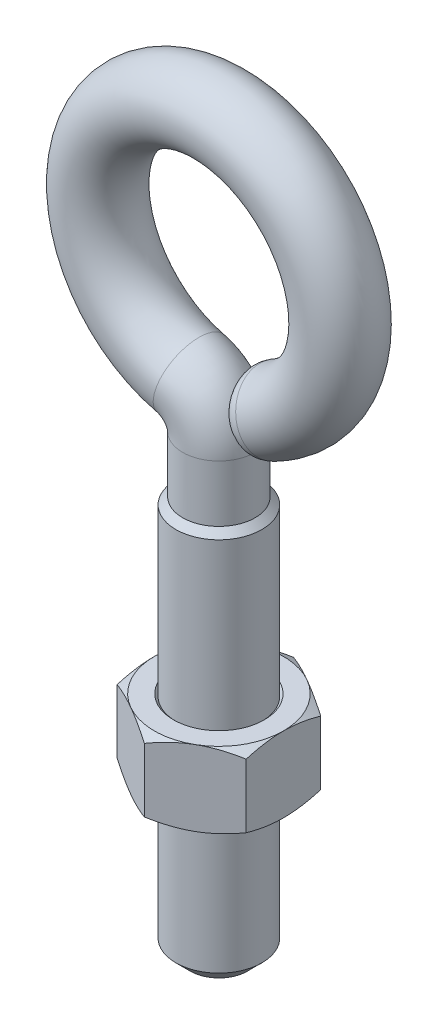
SolidWorks part; units mm, degrees
ref_plane "Front Plane" through (0, 0, 0) normal (0, 0, 1) x (1, 0, 0)
ref_plane "Top Plane" through (0, 0, 0) normal (0, 1, 0) x (1, 0, 0)
ref_plane "Right Plane" through (0, 0, 0) normal (1, 0, 0) x (0, 0, -1)
sketch "Sketch1" plane through (0, 0, 0) normal (0, 0, 1) x (1, 0, 0)
  line L0 (0, -8.636) -> (0, -34.036) construction
  line L1 (-2.413, -34.036) -> (2.413, -34.036) construction
  line L2 (0, -11.811) -> (2.413, -11.811) construction
  line L3 (0, -8.636) -> (0, -4.7625) construction
  line L4 (-2.032, -11.811) -> (2.032, -11.811) construction
  line L5 (2.032, -11.811) -> (2.032, -8.636) construction
  line L7 (2.413, -34.036) -> (2.413, -11.811) construction
  line L8 (2.032, -8.636) -> (0, -8.636) construction
  circle A0 centre (0, 0) radius 8.8265 construction
  circle A1 centre (0, 6.7945) radius 2.032 construction
  circle A2 centre (0, 0) radius 4.7625 construction
  point P9 (0, -8.636)
  point P10 (0, 8.8265)
  point P11 (0, 4.7625)
  point P14 (0, -34.036)
  point P24 (0, -11.811)
  dimension "A" = 4.064
  dimension "Eye Dia." = 9.525
  dimension "Shank Lg." = 25.4
  dimension "Thread OD" = 4.826
  dimension "Thread Lg." = 22.225
  dimension "Overall Lg." = 42.8625
  dimension "OD" = 17.4625
  dimension "Wire OD." = 4.064
sketch "Sketch2" plane through (0, 0, 0) normal (0, 1, 0) x (1, 0, 0)
  circle A0 centre (0, 0) radius 2.413
extrude "Boss-Extrude1" add sketch "Sketch2" against normal up to vertex (34.036 mm away) from vertex up to point (0, -34.036, 0) starting at point (0, -11.811, 0)
sketch "Sketch3" plane through (0, -34.036, 0) normal (0, -1, 0) x (1, 0, 0)
  circle A1 centre (0, 0) radius 2.413
  circle A2 centre (0, 0) radius 2.413
  point P0 (2.413, 0)
  point P1 (0, -2.413)
  dimension "D1" = 0
curve "Helix/Spiral1" [suppressed] pitch 1.0583 height 23.2833 turns 22 parameters "Pitch"=1.0583
sketch "Sketch4" plane through (0, 0, 0) normal (0, 0, 1) x (1, 0, 0)
  line L0 (2.5276, -33.9699) -> (2.5276, -35.0282) construction
  line L1 (2.5276, -35.0282) -> (1.611, -34.499) construction
  line L2 (1.611, -34.499) -> (2.5276, -33.9699) construction
  line L3 (1.7256, -34.4329) -> (1.7256, -34.5652) construction
  line L4 (2.413, -34.036) -> (2.413, -34.962) construction
  line L5 (1.611, -34.499) -> (1.7256, -34.499) construction
  line L6 (2.413, -34.499) -> (2.5276, -34.499) construction
  line L7 (2.4703, -34.0029) -> (1.7256, -34.4329)
  line L8 (1.7256, -34.4329) -> (1.7256, -34.5652)
  line L9 (1.7256, -34.5652) -> (2.4703, -34.9951)
  line L10 (2.4703, -34.9951) -> (2.4703, -34.0029)
  point P13 (2.4703, -34.499)
  dimension "D1" = 1.0583
  dimension "D2" = 0.1323
sweep "Cut-Sweep1" [suppressed] cut profiles "Sketch4" path "Helix/Spiral1"
sketch "Sketch5" plane through (0, -34.036, 0) normal (0, -1, 0) x (1, 0, 0)
  circle A0 centre (0, 0) radius 1.611
extrude "Cut-Extrude1" cut sketch "Sketch5" against normal up to vertex (22.225 mm away) draft 45 flip side to cut up to point (0, -11.811, 0)
sketch "Sketch7" plane through (0, -11.811, 0) normal (0, 1, 0) x (1, 0, 0)
  circle A0 centre (0, 0) radius 2.032
sketch "Sketch8" plane through (0, 0, 0) normal (0, 0, 1) x (1, 0, 0)
  line L0 (0, -8.636) -> (0, -34.036) construction
  line L1 (0, -8.636) -> (0, -11.811)
  line L2 (0, -8.636) -> (0, -4.7625) construction
  arc A0 (2.0092, -6.4906) -> (-1.599, -6.6037) centre (0, 0) ccw
  arc A1 (0, -8.636) -> (-1.599, -6.6037) centre (-2.091, -8.636) ccw
  circle A3 centre (0, -6.7945) radius 2.032 construction
sketch "Sketch6" plane through (0, -11.811, 0) normal (0, 1, 0) x (1, 0, 0)
  circle A0 centre (0, 0) radius 2.032
extrude "Cut-Extrude2" cut sketch "Sketch6" against normal up to vertex (22.225 mm away) draft 45 flip side to cut up to point (0, -34.036, 0)
sweep "Sweep1" add profiles "Sketch7" path "Sketch8"
fillet "Fillet1" radius 1.2065 1 edges at (2.0092, -6.4906, 2.032)
sketch "Sketch9" plane through (0, -34.036, 0) normal (0, -1, 0) x (1, 0, 0)
  line L1 (0, 4.1794) -> (-3.6195, 2.0897)
  line L2 (-3.6195, 2.0897) -> (-3.6195, -2.0897)
  line L3 (-3.6195, -2.0897) -> (0, -4.1794)
  line L4 (0, -4.1794) -> (3.6195, -2.0897)
  line L5 (3.6195, -2.0897) -> (3.6195, 2.0897)
  line L6 (3.6195, 2.0897) -> (0, 4.1794)
  circle A0 centre (0, 0) radius 3.6195 construction
  circle A1 centre (0, 0) radius 2.413
  dimension "Nut Wd." = 7.239
extrude "Boss-Extrude2" add sketch "Sketch9" against normal blind 4.2227 from offset 8.4455 separate body offset against normal yes
sketch "Sketch10" plane through (0, 0, 0) normal (1, 0, 0) x (0, 0, -1)
  line L0 (-3.6195, -21.3677) -> (-4.7394, -21.3677)
  line L1 (-4.7394, -21.3677) -> (-4.7394, -25.5905)
  line L2 (-4.7394, -25.5905) -> (-3.6195, -25.5905)
  line L3 (-3.6195, -25.5905) -> (-4.1794, -25.2672)
  line L4 (-4.1794, -25.2672) -> (-4.1794, -21.691)
  line L5 (-4.1794, -21.691) -> (-3.6195, -21.3677)
  line L6 (-2.2807, -21.3677) -> (-2.2807, -25.5905)
  line L7 (-2.2807, -25.5905) -> (-2.5453, -25.5905)
  line L8 (-2.5453, -25.5905) -> (-2.413, -25.4582)
  line L9 (-2.413, -25.4582) -> (-2.413, -21.5)
  line L10 (-2.413, -21.5) -> (-2.5453, -21.3677)
  line L11 (-2.5453, -21.3677) -> (-2.2807, -21.3677)
  line L12 (-2.413, -21.3677) -> (-2.413, -25.5905) construction
  line L14 (-2.413, -25.4582) -> (-2.413, -25.5905) construction
  line L15 (-2.413, -21.5) -> (-2.413, -21.3677) construction
  line L16 (-4.1794, -21.3677) -> (-4.1794, -25.5905) construction
  line L18 (-3.6195, -25.5905) -> (-3.6195, -34.036) construction
  dimension "D1" = 60
  dimension "D2" = 45
  dimension "D3" = 0.1323
revolve "Cut-Revolve1" cut sketch "Sketch10" angle 360 about L0
sketch "SketchX" plane through (0, 0, 0) normal (1, 0, 0) x (0, 0, -1)
  line L0 (2.413, -34.036) -> (2.413, -15.7797) construction
  dimension "D1" = 18.2562
equation "\"D3@Helix/Spiral1\" = \"Pitch@Helix/Spiral1\" + \"Thread Lg.@Sketch1\""
equation "\"D1@Sketch4\" = \"Pitch@Helix/Spiral1\""
equation "\"A@Sketch1\" = \"Wire OD.@Sketch1\""
equation "\"D2@Sketch4\" = \"D1@Sketch4\" / 8"
equation "\"D1@Fillet1\" = \"Thread OD@Sketch1\" / 4"
equation "\"D1@SketchX\" = \"Thread Lg.@Sketch1\" -  ( \"Pitch@Helix/Spiral1\" *  4 ) +  ( \"Pitch@Helix/Spiral1\" /  4 ) "
equation "\"Nut Wd.@Sketch9\" = \"Thread OD@Sketch1\" * 1.5"
equation "\"Nut Ht.@Boss-Extrude2\" = \"Thread OD@Sketch1\" * 0.875"
equation "\"Offset@Boss-Extrude2\" = \"Nut Ht.@Boss-Extrude2\" * 2"
equation "\"D3@Sketch10\" = \"Pitch@Helix/Spiral1\" / 8"
